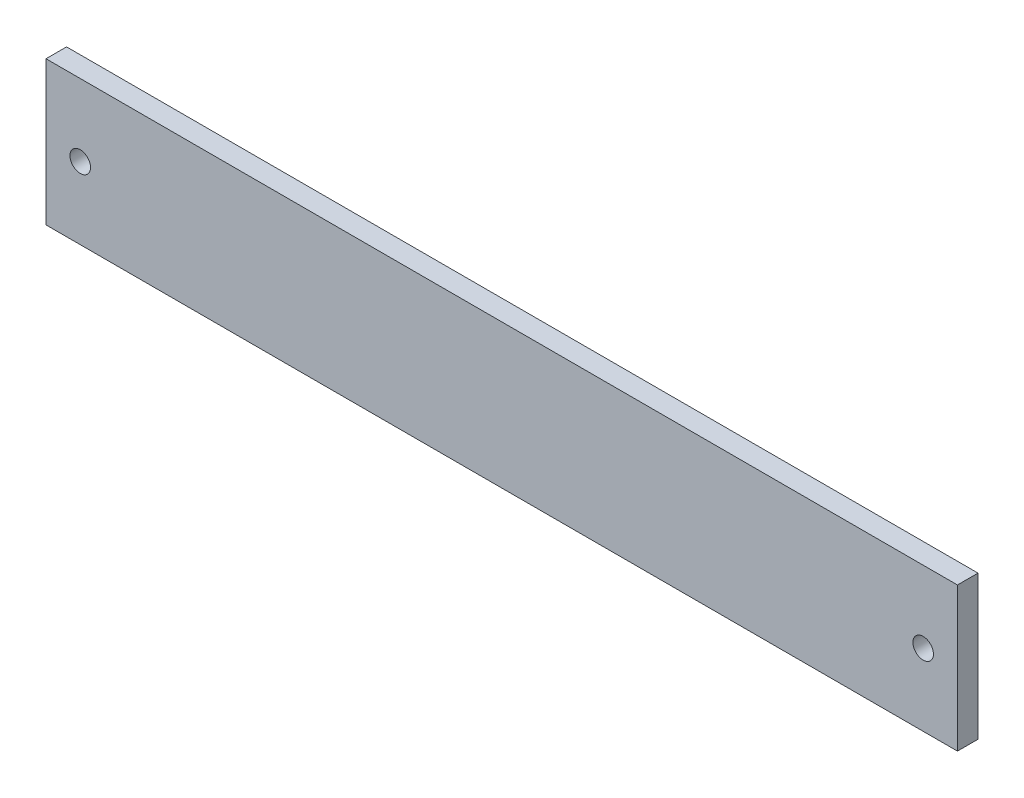
SolidWorks part; units mm, degrees
ref_plane "Front Plane" through (0, 0, 0) normal (0, 0, 1) x (1, 0, 0)
ref_plane "Top Plane" through (0, 0, 0) normal (0, 1, 0) x (1, 0, 0)
ref_plane "Right Plane" through (0, 0, 0) normal (1, 0, 0) x (0, 0, -1)
sketch "Sketch1" plane through (0, 0, 0) normal (0, 0, 1) x (1, 0, 0)
  line L1 (66.5, -10.5) -> (-66.5, -10.5)
  line L2 (66.5, -10.5) -> (66.5, 10.5)
  line L3 (66.5, 10.5) -> (-66.5, 10.5)
  line L4 (-66.5, -10.5) -> (-66.5, 10.5)
  line L5 (66.5, -10.5) -> (-66.5, 10.5) construction
  line L6 (66.5, 10.5) -> (-66.5, -10.5) construction
  circle A0 centre (-61.5, 0) radius 1.5
  circle A1 centre (61.5, 0) radius 1.5
  point P0 (0, 0)
  dimension "D3" = 3
  dimension "D4" = 5
  dimension "D5" = 5
  dimension "D6" = 3
  dimension "D7" = 10.5
  dimension "D1" = 21
  dimension "D2" = 133
extrude "Boss-Extrude1" add sketch "Sketch1" along normal blind 3
